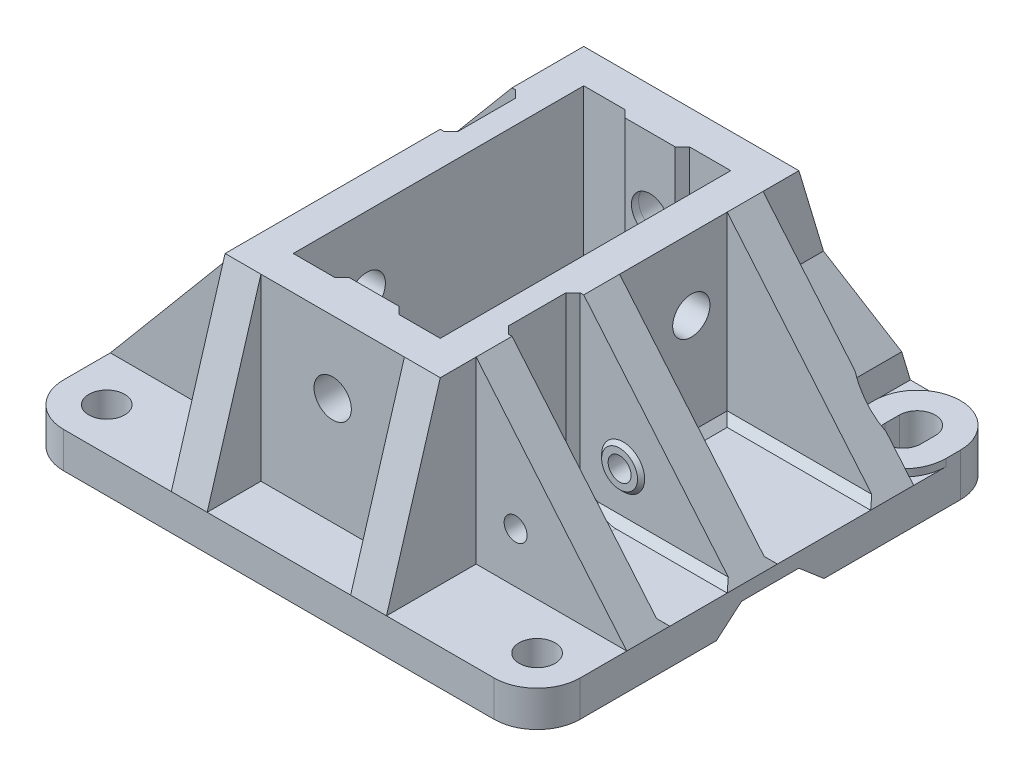
SolidWorks part; units mm, degrees
ref_plane "Front Plane" through (0, 0, 0) normal (0, 0, 1) x (1, 0, 0)
ref_plane "Top Plane" through (0, 0, 0) normal (0, 1, 0) x (1, 0, 0)
ref_plane "Right Plane" through (0, 0, 0) normal (1, 0, 0) x (0, 0, -1)
sketch "Sketch1" plane through (0, 0, 0) normal (0, 1, 0) x (1, 0, 0)
  line L0 (0, 0) -> (0, 65)
  line L1 (0, 0) -> (72, 0)
  line L2 (0, 65) -> (72, 65)
  line L3 (72, 0) -> (72, 65)
  dimension "D1" = 72
  dimension "D2" = 65
extrude "Boss-Extrude1" add sketch "Sketch1" along normal blind 5
sketch "Sketch2" plane through (0, 5, 0) normal (0, 1, 0) x (1, 0, 0)
  line L0 (21, 57.5) -> (21, 7.5)
  line L1 (21, 57.5) -> (51, 57.5)
  line L2 (21, 7.5) -> (51, 7.5)
  line L3 (51, 57.5) -> (51, 7.5)
  line L4 (0, 0) -> (72, 0) construction
  line L7 (72, 0) -> (72, 65) construction
  dimension "D1" = 50
  dimension "D2" = 7.5
  dimension "D3" = 30
  dimension "D4" = 21
extrude "Boss-Extrude2" add sketch "Sketch2" along normal blind 25
sketch "Sketch4" plane through (0, 30, 0) normal (0, 1, 0) x (1, 0, 0)
  line L0 (25.75, 52.75) -> (25.75, 12.25)
  line L1 (25.75, 52.75) -> (46.25, 52.75)
  line L2 (25.75, 12.25) -> (46.25, 12.25)
  line L3 (46.25, 52.75) -> (46.25, 12.25)
  line L4 (51, 57.5) -> (21, 57.5) construction
  line L6 (21, 57.5) -> (21, 7.5) construction
  dimension "D1" = 40.5
  dimension "D2" = 4.75
  dimension "D3" = 20.5
  dimension "D4" = 4.75
extrude "Cut-Extrude1" cut sketch "Sketch4" against normal blind 25
sketch "Sketch5" plane through (51, 0, 0) normal (1, 0, 0) x (0, 0, -1)
  line L0 (57.5, 30) -> (65, 5)
  line L1 (57.5, 5) -> (65, 5)
  line L2 (57.5, 5) -> (57.5, 30)
extrude "Boss-Extrude3" add sketch "Sketch5" against normal blind 5
ref_plane "Plane1" through (36, 0, 0) normal (1, 0, 0) x (0, 0, -1)
mirror "Mirror1" about plane through (36, 0, 0) normal (1, 0, 0) of "Boss-Extrude3"
ref_plane "Plane2" through (0, 0, -32.5) normal (0, 0, 1) x (1, 0, 0)
mirror "Mirror2" about plane through (0, 0, -32.5) normal (0, 0, 1) of "Mirror1", "Boss-Extrude3"
sketch "Sketch6" plane through (0, 0, -7.5) normal (0, 0, 1) x (1, 0, 0)
  line L0 (51, 30) -> (72, 5)
  line L1 (72, 5) -> (51, 5)
  line L2 (51, 5) -> (51, 30)
extrude "Boss-Extrude4" add sketch "Sketch6" against normal blind 5 from offset 5 offset against normal yes
mirror "Mirror3" about plane through (0, 0, -32.5) normal (0, 0, 1) of "Boss-Extrude4"
sketch "Sketch7" plane through (0, 0, -32.5) normal (0, 0, 1) x (1, 0, 0)
  line L0 (51, 30) -> (72, 5)
  line L1 (72, 5) -> (51, 5)
  line L2 (51, 5) -> (51, 30)
extrude "Boss-Extrude5" add sketch "Sketch7" along normal blind 5
mirror "Mirror4" about plane through (36, 0, 0) normal (1, 0, 0) of "Boss-Extrude4", "Mirror3"
sketch "Sketch8" plane through (0, 0, -32.5) normal (0, 0, 1) x (1, 0, 0)
  line L0 (21, 30) -> (0, 5)
  line L1 (0, 5) -> (21, 5)
  line L2 (21, 5) -> (21, 30)
extrude "Boss-Extrude6" add sketch "Sketch8" against normal blind 5
fillet "Fillet1" radius 6 4 edges at (0, 2.5, -65) (0, 2.5, 0) (72, 2.5, 0) (72, 2.5, -65)
sketch "Sketch9" plane through (0, 5, 0) normal (0, 1, 0) x (1, 0, 0)
  line L0 (63.5, 59) -> (63.5, 57)
  line L1 (68.5, 57) -> (68.5, 59)
  line L2 (60, 59) -> (60, 57)
  line L3 (72, 59) -> (72, 57)
  arc A1 (72, 59) -> (60, 59) centre (66, 59) ccw
  arc A2 (63.5, 57) -> (68.5, 57) centre (66, 57) ccw
  arc A3 (68.5, 59) -> (63.5, 59) centre (66, 59) ccw
  arc A4 (72, 59) -> (66, 65) centre (66, 59) ccw construction
  arc A6 (60, 57) -> (72, 57) centre (66, 57) ccw
  point P1 (68.5, 58)
  point P3 (72, 58)
  point P4 (66, 61.5)
  dimension "D1" = 12
  dimension "D2" = 12
  dimension "D3" = 5
  dimension "D4" = 5
  dimension "D5" = 2
  dimension "D6" = 2
  dimension "D7" = 2
  dimension "D8" = 3.5
  dimension "D9" = 3.5
sketch "Sketch10" plane through (72, 0, 0) normal (1, 0, 0) x (0, 0, -1)
  line L0 (36.5, 3) -> (32.5, 3)
  line L1 (0, 0) -> (65, 0) construction
  line L2 (32.5, 5) -> (47.5, 5) construction
  line L3 (36.5, 3) -> (40, 0)
  line L5 (32.5, 5) -> (32.5, 30) construction
  line L6 (28.5, 3) -> (25, 0)
  line L7 (28.5, 3) -> (32.5, 3)
  line L8 (25, 0) -> (40, 0)
  line M7 (6, 0) -> (59, 0)
  dimension "D1" = 4
  dimension "D2" = 25
  dimension "D3" = 3.5
  dimension "D4" = 2
extrude "Cut-Extrude3" cut sketch "Sketch10" against normal blind 75 contours L7 L6 L3 L0 M7 region at (72, 1.3478, -32.5)
sketch "Sketch11" plane through (0, 5, 0) normal (0, 1, 0) x (1, 0, 0)
  line L0 (51, 0) -> (66, 0) construction
  line L1 (72, 0) -> (72, 65) construction
  circle A0 centre (66, 6) radius 2.5
  dimension "D1" = 5
  dimension "D2" = 6
  dimension "D3" = 6
extrude "Cut-Extrude4" cut sketch "Sketch11" against normal blind 5
mirror "Mirror6" about plane through (36, 0, 0) normal (1, 0, 0) of "Cut-Extrude4"
sketch "Sketch12" plane through (0, 0, -12.5) normal (0, 0, 1) x (1, 0, 0)
  line L0 (51, 30) -> (51, 5) construction
  line L1 (51, 5) -> (72, 5) construction
  circle A0 centre (56.5, 12) radius 1.6
  dimension "D1" = 3.2
  dimension "D2" = 5.5
  dimension "D3" = 7
extrude "Cut-Extrude5" cut sketch "Sketch12" against normal blind 5
sketch "Sketch13" plane through (0, 0, -7.5) normal (0, 0, 1) x (1, 0, 0)
  line L0 (26, 30) -> (46, 30) construction
  line L1 (46, 5) -> (46, 30) construction
  circle A0 centre (36, 20) radius 2.6021
  dimension "D1" = 5.2043
  dimension "D2" = 10
  dimension "D3" = 10
extrude "Cut-Extrude6" cut sketch "Sketch13" against normal blind 7
sketch "Sketch14" plane through (0, 0, -12.25) normal (0, 0, -1) x (-1, 0, 0)
  line L0 (-32.5, 30) -> (-32.5, 5)
  line L1 (-32.5, 30) -> (-39.5, 30)
  line L2 (-32.5, 5) -> (-39.5, 5)
  line L3 (-39.5, 30) -> (-39.5, 5)
  line L4 (-25.75, 30) -> (-46.25, 30) construction
  line L5 (-25.75, 5) -> (-46.25, 5) construction
  dimension "D1" = 7
  dimension "D2" = 6.75
extrude "Boss-Extrude7" add sketch "Sketch14" along normal blind 1
sketch "Sketch15" plane through (0, 30, 0) normal (0, 1, 0) x (1, 0, 0)
  line L0 (39.5, 13.25) -> (40.5, 12.25)
  line L1 (39.5, 12.25) -> (46.25, 12.25) construction
  line L2 (40.5, 12.25) -> (39.5, 12.25)
  line L3 (39.5, 12.25) -> (39.5, 13.25)
  dimension "D1" = 1
extrude "Boss-Extrude8" add sketch "Sketch15" against normal blind 25
mirror "Mirror7" about plane through (36, 0, 0) normal (1, 0, 0) of "Boss-Extrude8"
mirror "Mirror8" about plane through (0, 0, -32.5) normal (0, 0, 1) of "Cut-Extrude6", "Boss-Extrude7", "Mirror7"
sketch "Sketch16" plane through (0, 0, -12.25) normal (0, 0, 1) x (1, 0, 0)
  circle A0 centre (36, 20) radius 2.6
  dimension "D1" = 5.2
extrude "Cut-Extrude7" cut sketch "Sketch16" against normal blind 65
ref_plane "Plane3" through (72, 5, -52.5) normal (0, 0, -1) x (-1, 0, 0)
sketch "Sketch21" plane through (0, 30, 0) normal (0, 1, 0) x (1, 0, 0)
  line L0 (21.5, 47.5) -> (22.5, 46.5)
  line L1 (22.5, 46.5) -> (22.5, 38.5)
  line L2 (21, 47.5) -> (21.5, 47.5)
  line L3 (21, 47.5) -> (21, 37.5) construction
  line L4 (21, 47.5) -> (21, 37.5)
  line L5 (21.5, 37.5) -> (22.5, 38.5)
  line L6 (21, 37.5) -> (21.5, 37.5)
  point P9 (21, 42.5)
  dimension "D2" = 0.5
  dimension "D3" = 135
extrude "Cut-Extrude8" cut sketch "Sketch21" against normal blind 25 and the other way through all
fillet "Fillet5" radius 7 1 edges at (22.5, 5, -42.5) type face fillet first side face at (14.6667, 5, -42.5) second side face at (22.5, 17.5, -42.5)
sketch "Sketch22" plane through (0, 30, 0) normal (0, 1, 0) x (1, 0, 0)
  line L0 (51, 17.5) -> (50.4994, 17.5)
  line L1 (50.4994, 17.5) -> (49.4994, 18.5)
  line L2 (49.4994, 18.5) -> (49.4994, 26.5)
  line L5 (51, 27.5) -> (50.4994, 27.5)
  line L6 (50.4994, 27.5) -> (49.4994, 26.5)
  line L7 (51, 17.5) -> (51, 27.5)
  dimension "D1" = 0.5006
  dimension "D2" = 1
  dimension "D3" = 135
extrude "Cut-Extrude9" cut sketch "Sketch22" against normal blind 25
fillet "Fillet6" radius 7 1 edges at (49.4994, 5, -22.5) type face fillet first side face at (57.3329, 5, -22.5) second side face at (49.4994, 17.5, -22.5)
sketch "Sketch23" plane through (72, 0, 0) normal (1, 0, 0) x (0, 0, -1)
  line L0 (17.5, 5) -> (17.5, 5.9984)
  line L1 (17.5, 5) -> (18.5023, 5)
  line L2 (17.5, 5) -> (27.5, 5) construction
  line L3 (18.5023, 5) -> (17.5, 5.9984)
extrude "Boss-Extrude10" add sketch "Sketch23" against normal blind 25
sketch "Sketch24" plane through (72, 0, 0) normal (1, 0, 0) x (0, 0, -1)
  line L0 (27.5, 5) -> (27.5, 6)
  line L1 (27.5, 6) -> (26.5, 5)
  line L2 (18.5023, 5) -> (27.5, 5) construction
  line L3 (26.5, 5) -> (27.5, 5)
  dimension "D1" = 1
  dimension "D2" = 1
extrude "Boss-Extrude11" add sketch "Sketch24" against normal blind 25
sketch "Sketch25" plane through (0, 0, -32.5) normal (0, 0, -1) x (-1, 0, 0)
  line L0 (-51, 5) -> (-51, 5.9978)
  line L1 (-51, 30) -> (-51, 5) construction
  line L2 (-51, 5.9978) -> (-52, 5)
  line L3 (-51, 5) -> (-72, 5) construction
  line L4 (-52, 5) -> (-51, 5)
  dimension "D1" = 1
extrude "Boss-Extrude12" add sketch "Sketch25" along normal blind 15
sketch "Sketch26" plane through (72, 0, 0) normal (1, 0, 0) x (0, 0, -1)
  line L0 (32.5, 5) -> (32.5, 5.9972)
  line L1 (32.5, 5.9972) -> (33.5, 5)
  line L2 (32.5, 5) -> (47.5, 5) construction
  line L3 (33.5, 5) -> (32.5, 5)
  dimension "D1" = 1
extrude "Boss-Extrude13" add sketch "Sketch26" against normal blind 25
sketch "Sketch27" plane through (72, 0, 0) normal (1, 0, 0) x (0, 0, -1)
  line L0 (47.5, 5) -> (47.5, 6)
  line L1 (47.5, 6) -> (46.5, 5)
  line L2 (33.5, 5) -> (47.5, 5) construction
  line L3 (46.5, 5) -> (47.5, 5)
  dimension "D1" = 1
  dimension "D2" = 1
extrude "Boss-Extrude14" add sketch "Sketch27" against normal blind 25
ref_plane "Plane4" through (44.6764, 37.5281, 0) normal (0.7657, 0.6432, 0) x (0, 0, -1)
sketch "Sketch28" plane through (44.6764, 37.5281, 0) normal (0.7657, 0.6432, 0) x (0, 0, -1)
  line L0 (11.4122, -43.5785) -> (50.5755, -43.5785)
  line L1 (11.4122, -43.5785) -> (11.4122, -35.2711)
  line L2 (50.5755, -43.5785) -> (50.5755, -35.2711)
  line L3 (11.4122, -35.2711) -> (50.5755, -35.2711)
extrude "Cut-Extrude10" cut sketch "Sketch28" along normal blind 5
sketch "Sketch29" plane through (0, 0, 0) normal (-1, 0, 0) x (0, 0, 1)
  line L0 (-47.5, 5) -> (-47.5, 6)
  line L1 (-47.5, 6) -> (-46.5, 5)
  line L2 (-47.5, 5) -> (-37.5, 5) construction
  line L3 (-46.5, 5) -> (-47.5, 5)
  line L4 (-37.5, 5) -> (-37.5, 6)
  line L5 (-37.5, 6) -> (-38.5, 5)
  line L6 (-38.5, 5) -> (-37.5, 5)
  dimension "D1" = 1
  dimension "D2" = 1
  dimension "D3" = 1
  dimension "D4" = 1
extrude "Boss-Extrude15" add sketch "Sketch29" against normal blind 25
sketch "Sketch30" plane through (0, 0, -32.5) normal (0, 0, 1) x (1, 0, 0)
  line L0 (21, 5) -> (20, 5)
  line L1 (0, 5) -> (21, 5) construction
  line L2 (20, 5) -> (21, 6)
  line L3 (21, 5) -> (21, 30) construction
  line L4 (21, 6) -> (21, 5)
  dimension "D1" = 1
  dimension "D2" = 1
extrude "Boss-Extrude16" add sketch "Sketch30" along normal blind 15
sketch "Sketch31" plane through (0, 0, 0) normal (-1, 0, 0) x (0, 0, 1)
  line L0 (-32.5, 5) -> (-32.5, 6)
  line L1 (-32.5, 6) -> (-31.5, 5)
  line L2 (-32.5, 5) -> (-17.5, 5) construction
  line L3 (-31.5, 5) -> (-32.5, 5)
  line L4 (-17.5, 5) -> (-17.5, 6.0006)
  line L5 (-17.5, 6.0006) -> (-18.5006, 5)
  line L6 (-18.5006, 5) -> (-17.5, 5)
  dimension "D1" = 1.0006
  dimension "D2" = 1.0006
  dimension "D3" = 1
  dimension "D4" = 1
extrude "Boss-Extrude17" add sketch "Sketch31" against normal blind 25
mirror "Mirror10" about plane through (36, 0, 0) normal (1, 0, 0) of "Cut-Extrude10"
sketch "Sketch32" plane through (0, 0, -17.5) normal (0, 0, -1) x (-1, 0, 0)
  circle A0 centre (-56.5, 12) radius 3
  dimension "D1" = 6
extrude "Boss-Extrude18" add sketch "Sketch32" along normal blind 0.5 draft 45
sketch "Sketch33" plane through (0, 0, -12.5) normal (0, 0, 1) x (1, 0, 0)
  circle A0 centre (56.5, 12) radius 1.6
extrude "Cut-Extrude11" cut sketch "Sketch33" against normal blind 20.5
sketch "Sketch34" plane through (0, 0, -27.5) normal (0, 0, 1) x (1, 0, 0)
  circle A0 centre (56.5, 12) radius 3
  dimension "D1" = 6
extrude "Boss-Extrude19" add sketch "Sketch34" along normal blind 0.5 draft 45
sketch "Sketch35" plane through (0, 0, -32.5) normal (0, 0, -1) x (-1, 0, 0)
  circle A0 centre (-56.5, 12) radius 1.6
extrude "Cut-Extrude12" cut sketch "Sketch35" against normal blind 10.5
sketch "Sketch36" plane through (0, 0, -52.5) normal (0, 0, -1) x (-1, 0, 0)
  line L0 (-21, 30) -> (-21, 5) construction
  line L1 (-21, 5) -> (0, 5) construction
  circle A0 centre (-15.5, 12) radius 1.6
  dimension "D1" = 3.2
  dimension "D2" = 5.5
  dimension "D3" = 7
sketch "Sketch37" plane through (0, 0, -47.5) normal (0, 0, 1) x (1, 0, 0)
  circle A0 centre (15.5, 12) radius 3
  dimension "D1" = 6
extrude "Boss-Extrude20" add sketch "Sketch37" along normal blind 0.5 draft 45
sketch "Sketch38" plane through (0, 0, -37.5) normal (0, 0, -1) x (-1, 0, 0)
  circle A0 centre (-15.5, 12) radius 3
  dimension "D1" = 6
extrude "Boss-Extrude21" add sketch "Sketch38" along normal blind 0.5 draft 45
extrude "Cut-Extrude13" cut sketch "Sketch36" against normal blind 20.5
sketch "Sketch40" plane through (21, 0, 0) normal (-1, 0, 0) x (0, 0, 1)
  line L1 (-32.5, 30) -> (-17.5, 30) construction
  line L2 (-17.5, 30) -> (-17.5, 6.0006) construction
  circle A0 centre (-22.5, 20) radius 2.6
  dimension "D1" = 5.2
  dimension "D3" = 5
  dimension "D2" = 10
extrude "Cut-Extrude14" cut sketch "Sketch40" against normal blind 10
sketch "Sketch41" plane through (51, 0, 0) normal (1, 0, 0) x (0, 0, -1)
  line L0 (32.5, 30) -> (47.5, 30) construction
  line L1 (47.5, 30) -> (47.5, 6) construction
  circle A0 centre (42.5, 20) radius 2.6
  point P4 (40, 30)
  dimension "D1" = 5.2
  dimension "D2" = 10
  dimension "D3" = 5
extrude "Cut-Extrude15" cut sketch "Sketch41" against normal blind 10
extrude "Boss-Extrude22" add sketch "Sketch9" along normal blind 1
sketch "Sketch42" plane through (0, 6, 0) normal (0, 1, 0) x (1, 0, 0)
  line L0 (66, 65) -> (72, 65)
  line L1 (72, 65) -> (59.4165, 65)
  arc A0 (72, 59) -> (60, 59) centre (66, 59) ccw construction
ref_plane "Plane5" through (0, 0.8221, 0.0654) normal (0, 0.9968, 0.0793) x (-1, 0, 0)
sketch "Sketch45" plane through (0, 6, 0) normal (0, 1, 0) x (1, 0, 0)
  line L0 (68.1794, 52.5) -> (63.8076, 52.5063)
  line L1 (62.0314, 52.5) -> (69.9686, 52.5) construction
  arc A0 (63.8076, 52.5063) -> (68.1794, 52.5) centre (66, 57) ccw
  dimension "D1" = 10
extrude "Cut-Extrude17" cut sketch "Sketch45" along normal blind 11
sketch "Sketch47" plane through (0, 5, 0) normal (0, 1, 0) x (1, 0, 0)
  line L0 (68.5, 59) -> (68.5, 57)
  line L1 (63.5, 57) -> (63.5, 59)
  arc A0 (63.5, 57) -> (68.5, 57) centre (66, 57) ccw
  arc A1 (68.5, 59) -> (63.5, 59) centre (66, 59) ccw
extrude "Cut-Extrude18" cut sketch "Sketch47" against normal blind 10
mirror "Mirror12" about plane through (36, 0, 0) normal (1, 0, 0) of "Cut-Extrude17", "Boss-Extrude22"
sketch "Sketch48" plane through (0, 0, -52.5) normal (0, 0, -1) x (-1, 0, 0)
  line L0 (-59.0348, 5) -> (-59.0348, 9)
  line L2 (-59.0348, 9) -> (-51, 18.5756)
  line L4 (-51, 5) -> (-62.0314, 5) construction
  line L5 (-51, 5) -> (-59.0348, 5)
  line L12 (-51, 18.5756) -> (-51, 5)
  dimension "D1" = 140
  dimension "D2" = 4
  dimension "D3" = 12.5
extrude "Boss-Extrude23" add sketch "Sketch48" along normal blind 12.5
ref_plane "Plane6" through (0, 18.3028, -61.0092) normal (0, 0.2873, -0.9578) x (-1, 0, 0)
sketch "Sketch49" plane through (0, 18.3028, -61.0092) normal (0, 0.2873, -0.9578) x (-1, 0, 0)
  line L0 (-61.8582, -14.6362) -> (-61.8582, 7.6102)
  line L1 (-61.8582, -14.6362) -> (-48.4009, -14.6362)
  line L2 (-61.8582, 7.6102) -> (-48.4009, 7.6102)
  line L3 (-48.4009, -14.6362) -> (-48.4009, 7.6102)
sketch "Sketch50" plane through (0, 0, -65) normal (0, 0, -1) x (-1, 0, 0)
  line L0 (-59.0348, 9) -> (-59.0348, 5) construction
  line L1 (-66, 5) -> (-59.0348, 5) construction
  circle A0 centre (-52.5348, 7) radius 2
  point P4 (-59.0348, 7)
  dimension "D1" = 4
  dimension "D2" = 6.5
extrude "Cut-Extrude20" cut sketch "Sketch50" against normal blind 12.5
extrude "Cut-Extrude21" cut sketch "Sketch49" along normal blind 12.5
